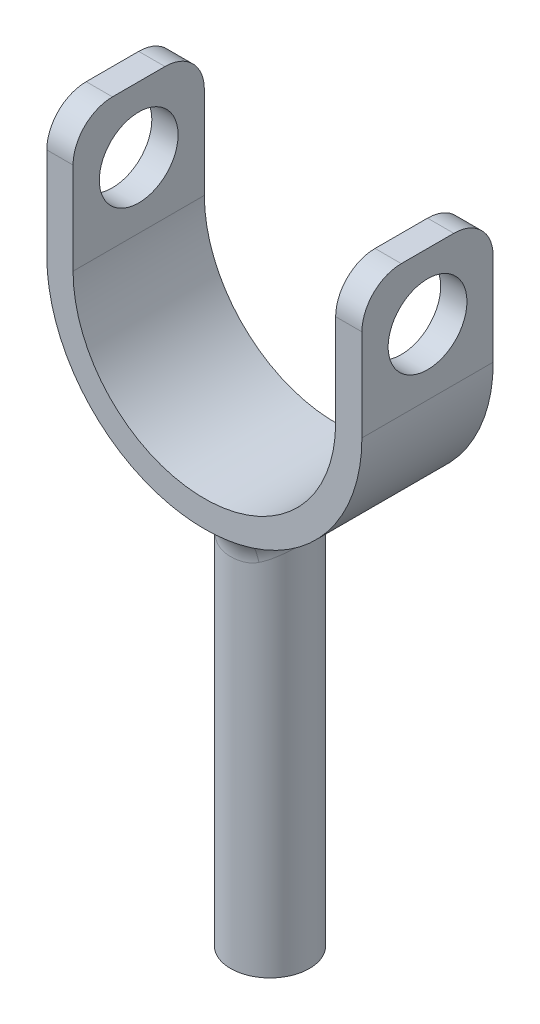
SolidWorks part; units mm, degrees
ref_plane "Alzado" through (0, 0, 0) normal (0, 0, 1) x (1, 0, 0)
ref_plane "Planta" through (0, 0, 0) normal (0, 1, 0) x (1, 0, 0)
ref_plane "Vista lateral" through (0, 0, 0) normal (1, 0, 0) x (0, 0, -1)
sketch "Croquis1" plane through (0, 0, 0) normal (0, 0, 1) x (1, 0, 0)
  line L0 (-60, 110) -> (-60, 60)
  line L1 (0, 0) -> (-216.3462, 0) construction
  line L2 (0, 0) -> (0, 239.4231) construction
  line L3 (-50, 110) -> (-50, 60)
  line L4 (-60, 110) -> (-50, 110)
  line L5 (0, 0) -> (0, 10) construction
  line L6 (60, 110) -> (50, 110)
  line L7 (50, 110) -> (50, 60)
  line L8 (60, 110) -> (60, 60)
  arc A0 (-60, 60) -> (0, 0) centre (0, 60) ccw
  arc A1 (-50, 60) -> (0, 10) centre (0, 60) ccw
  arc A2 (60, 60) -> (0, 0) centre (0, 60) cw
  arc A3 (50, 60) -> (0, 10) centre (0, 60) cw
  dimension "D1" = 50
  dimension "D2" = 60
  dimension "D3" = 10
extrude "Saliente-Extruir1" add sketch "Croquis1" along normal mid plane 50 contours L7 A3 A1 L3 L4 L0 A0 A2 L8 L6 region at (-55, 108.3721, 0)
sketch "Croquis3" plane through (0, 0, 0) normal (0, 0, 1) x (1, 0, 0)
  line L0 (0, 1.9052) -> (0, -150)
  line L1 (0, -150) -> (15, -150)
  line L2 (15, -150) -> (15, 1.9052)
  line L3 (15, 1.9052) -> (0, 1.9052)
  arc A0 (-60, 60) -> (60, 60) centre (0, 60) ccw construction
  dimension "D1" = 15
  dimension "D2" = 210
revolve "Revolución2" add sketch "Croquis3" angle 360 about L0
fillet "Redondeo1" radius 15 1 edges at (14.7095, 1.831, 2.9378)
fillet "Redondeo2" radius 15 4 edges at (-55, 110, -25) (-55, 110, 25) (55, 110, -25) (55, 110, 25)
hole_wizard "Taladro1" positions "Croquis6" profile "Croquis7" legacy end condition through all
sketch "Croquis6" plane through (60, 0, 0) normal (1, 0, 0) x (0, 0, -1)
  line L0 (-10, 110) -> (10, 110) construction
  point P0 (0, 85)
  dimension "D1" = 25
sketch "Croquis7" plane through (60, 85, 0) normal (0, 1, 0) x (0, 0, -1)
  line L0 (0, 0) -> (0, 120)
  line L1 (0, 120) -> (15, 120)
  line L2 (15, 120) -> (15, 0)
  line L3 (15, 0) -> (0, 0)
  line L4 (0, 110) -> (0, -10) construction
  dimension "Diámetro" = 30
  dimension "Profundidad" = 120
